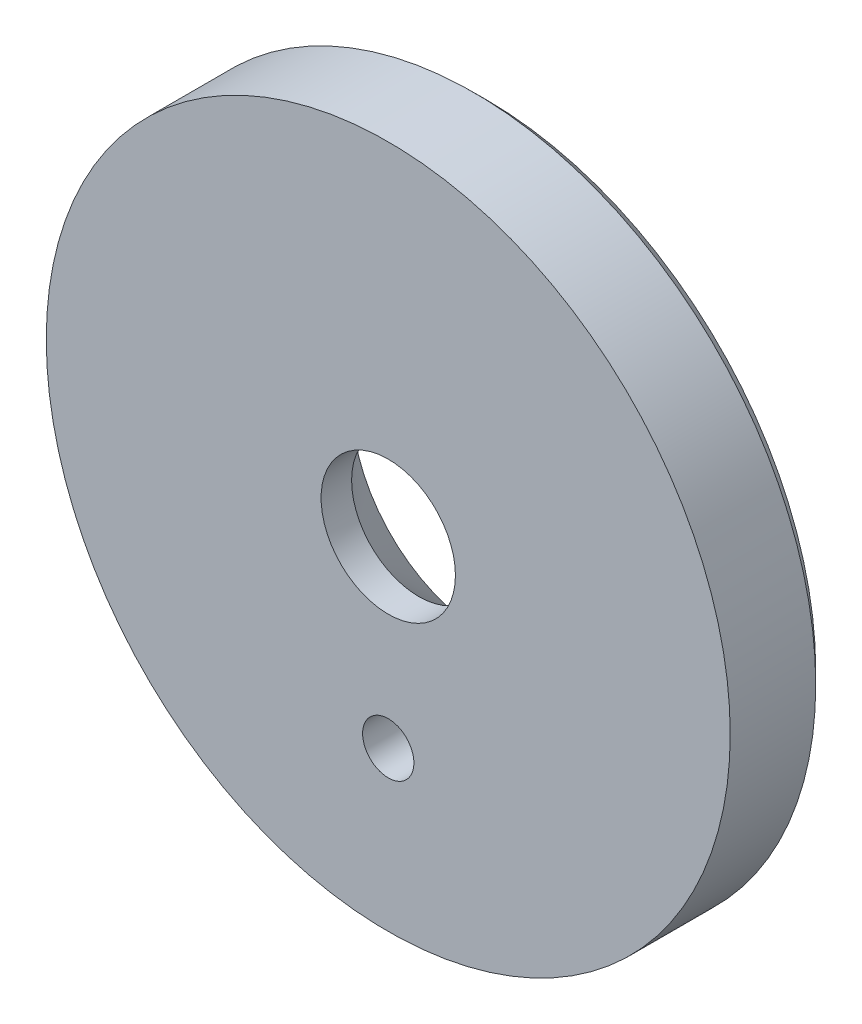
SolidWorks part; units mm, degrees
ref_plane "Front" through (0, 0, 0) normal (0, 0, 1) x (1, 0, 0)
ref_plane "Top" through (0, 0, 0) normal (0, 1, 0) x (1, 0, 0)
ref_plane "Right" through (0, 0, 0) normal (1, 0, 0) x (0, 0, -1)
sketch "Sketch1" plane through (0, 0, 0) normal (0, 0, 1) x (1, 0, 0)
  circle A0 centre (0, 0) radius 14
  circle A1 centre (0, 0) radius 2.75
  dimension "D0" = 28
  dimension "d" = 5.5
extrude "Base-Extrude" add sketch "Sketch1" against normal blind 4
sketch "Sketch2" plane through (0, 0, 0) normal (0, 1, 0) x (1, 0, 0)
  line L0 (-5.5, 4) -> (-2.75, 4)
  line L2 (-2.75, 4) -> (-2.75, 1.25)
  line L3 (-2.75, 1.25) -> (-5.5, 4)
  line L5 (0, 8.4656) -> (0, -7.9977) construction
  line L6 (-2.75, 4) -> (-2.75, 0) construction
  line L7 (14, 4) -> (-14, 4) construction
  dimension "D1" = 11
  dimension "a" = 45
revolve "Cut-Revolve1" cut sketch "Sketch2" angle 360 about L5
chamfer "Chamfer1" distance 0.5 angle 45 1 edges at (14, 0, -4)
sketch "Sketch3" plane through (-5.3213, -16.4716, -4) normal (0, 0, -1) x (-1, 0, 0)
  circle A0 centre (-5.3213, 8.9716) radius 1.05
  dimension "d1" = 2.1
  dimension "L" = 7.5
extrude "Hole-Exscind" cut sketch "Sketch3" against normal through all
